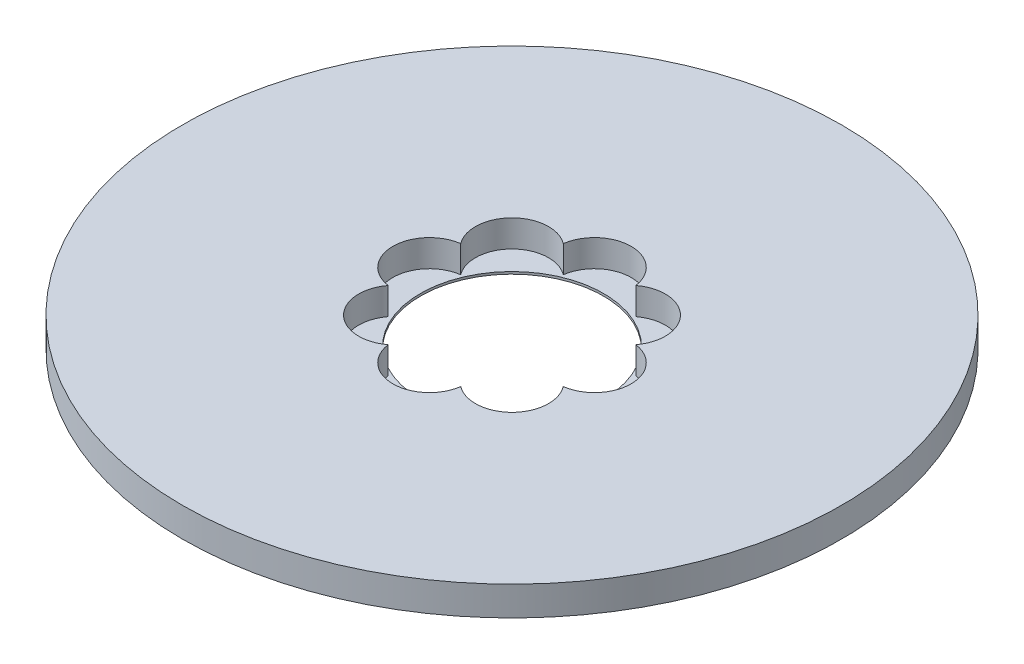
SolidWorks part; units mm, degrees
ref_plane "Front Plane" through (0, 0, 0) normal (0, 0, 1) x (1, 0, 0)
ref_plane "Top Plane" through (0, 0, 0) normal (0, 1, 0) x (1, 0, 0)
ref_plane "Right Plane" through (0, 0, 0) normal (1, 0, 0) x (0, 0, -1)
sketch "Sketch1" plane through (0, 0, 0) normal (0, 1, 0) x (1, 0, 0)
  circle A0 centre (0, 0) radius 90
  dimension "FLANGE_OD" = 180
extrude "Boss-Extrude1" add sketch "Sketch1" along normal blind 8
sketch "Sketch2" plane through (0, 0, 0) normal (0, 1, 0) x (1, 0, 0)
  circle A0 centre (0, 0) radius 25
  dimension "BORE_D" = 50
extrude "Cut-Extrude1" cut sketch "Sketch2" along normal through all
sketch "Sketch3" plane through (0, 8, 0) normal (0, 1, 0) x (1, 0, 0)
  circle A0 centre (0, 0) radius 22.5344 construction
  circle A1 centre (-22.5344, 0) radius 10
  dimension "BOLT_D" = 20
  dimension "BOLT_PCD" = 45.0688
extrude "Cut-Extrude2" cut sketch "Sketch3" against normal blind 7.3689
pattern_circular "CirPattern1" count 8 over 360 about axis through (0, 0, 0) along (0, 1, 0) of "Cut-Extrude2"
